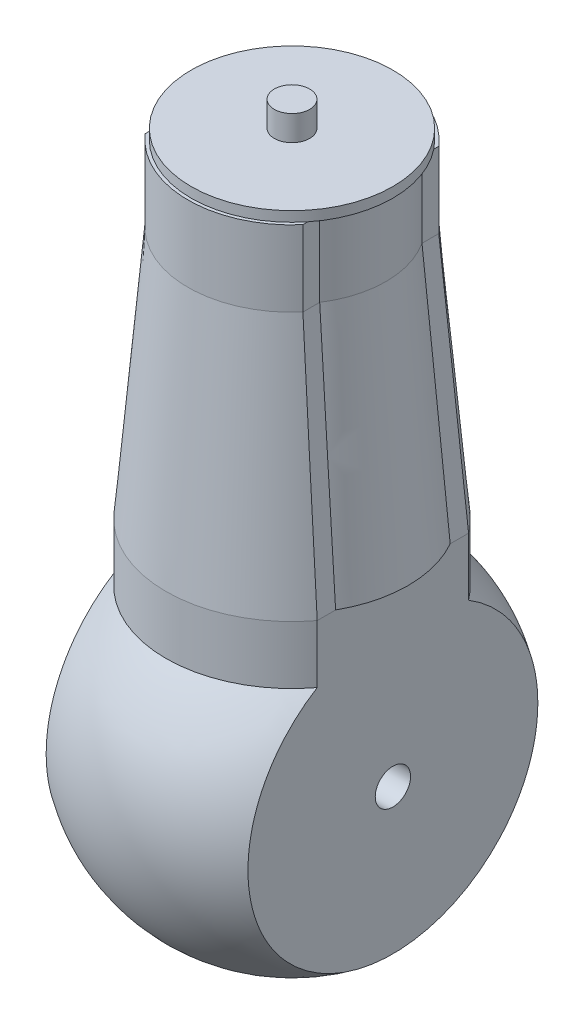
SolidWorks part; units mm, degrees
ref_plane "Front Plane" through (0, 0, 0) normal (0, 0, 1) x (1, 0, 0)
ref_plane "Top Plane" through (0, 0, 0) normal (0, 1, 0) x (1, 0, 0)
ref_plane "Right Plane" through (0, 0, 0) normal (1, 0, 0) x (0, 0, -1)
sketch "Sketch1" plane through (0, 0, 0) normal (0, 1, 0) x (1, 0, 0)
  line L0 (0, 35) -> (0, -35) construction
  line L1 (0, 35) -> (0, -35)
  arc A0 (0, -35) -> (0, 35) centre (0, 0) ccw
  dimension "D1" = 70
revolve "Revolve2" add sketch "Sketch1" angle 360 about L0
sketch "Sketch2" plane through (0, 0, 0) normal (0, 1, 0) x (1, 0, 0)
  line L2 (-20, -28.7228) -> (-20, 28.7228)
  line L4 (20, -28.7228) -> (20, 28.7228)
  line L5 (-20, -35) -> (20, 35) construction
  line L6 (-20, 35) -> (20, -35) construction
  arc A0 (20, 28.7228) -> (-20, 28.7228) centre (0, 0) ccw
  arc A1 (-20, -28.7228) -> (20, -28.7228) centre (0, 0) ccw
  dimension "D1" = 40
extrude "Cut-Extrude1" cut sketch "Sketch2" against normal up to next and the other way up to next flip side to cut
sketch "Sketch3" plane through (0, 0, 0) normal (0, 1, 0) x (1, 0, 0)
  line L4 (20, -28.7228) -> (20, 28.7228) construction
  line L6 (-20, 15) -> (-20, -15)
  line L8 (20, 15) -> (20, -15)
  line L9 (-20, 26.2775) -> (20, -26.2775) construction
  line L10 (-20, -26.2775) -> (20, 26.2775) construction
  arc A3 (20, 15) -> (-20, 15) centre (0, 0) ccw
  arc A4 (-20, -15) -> (20, -15) centre (0, 0) ccw
  arc A6 (-20, -28.7228) -> (20, -28.7228) centre (0, 0) ccw construction
  dimension "D1" = 50
  dimension "D2" = 10
extrude "Boss-Extrude1" add sketch "Sketch3" along normal blind 36
sketch "Sketch4" plane through (-20, 0, 0) normal (-1, 0, 0) x (0, 0, 1)
  circle A0 centre (0, 0) radius 3.5
  dimension "D1" = 7
extrude "Cut-Extrude2" cut sketch "Sketch4" against normal blind 5
pattern_linear "LPattern1" count 2 spacing 35 along (1, 0, 0) of "Cut-Extrude2"
sketch "Sketch5" plane through (0, 36, 0) normal (0, 1, 0) x (1, 0, 0)
  line L0 (-20, 15) -> (-20, 11.3578)
  line L1 (-20, 15) -> (-20, -15) construction
  line L2 (-20, -15) -> (-20, -11.3578)
  line L3 (20, 15) -> (20, 11.3578)
  line L4 (20, -11.3578) -> (20, -15)
  arc A0 (-20, -15) -> (20, -15) centre (0, 0) ccw
  arc A1 (20, -11.3578) -> (20, 11.3578) centre (0, 0) ccw
  arc A2 (20, 15) -> (-20, 15) centre (0, 0) ccw
  arc A3 (-20, 11.3578) -> (-20, -11.3578) centre (0, 0) ccw
  dimension "D2" = 46
extrude "Boss-Extrude2" add sketch "Sketch5" along normal blind 50 draft 5
sketch "Sketch9" plane through (0, 86, 0) normal (0, 1, 0) x (1, 0, 0)
  line L4 (15.6256, 10.1367) -> (15.6256, 13.4631)
  line L5 (-15.6256, 13.4631) -> (-15.6256, 10.1367)
  line L6 (-15.6256, -10.1367) -> (-15.6256, -13.4631)
  line L7 (15.6256, -13.4631) -> (15.6256, -10.1367)
  line L8 (15.6256, 10.1367) -> (15.6256, 13.4631)
  line L9 (-15.6256, 13.4631) -> (-15.6256, 10.1367)
  line L10 (-15.6256, -10.1367) -> (-15.6256, -13.4631)
  line L11 (15.6256, -13.4631) -> (15.6256, -10.1367)
  arc A4 (15.6256, -10.1367) -> (15.6256, 10.1367) centre (0, 0) ccw
  arc A5 (15.6256, 13.4631) -> (-15.6256, 13.4631) centre (0, 0) ccw
  arc A6 (-15.6256, 10.1367) -> (-15.6256, -10.1367) centre (0, 0) ccw
  arc A7 (-15.6256, -13.4631) -> (15.6256, -13.4631) centre (0, 0) ccw
  arc A8 (15.6256, -10.1367) -> (15.6256, 10.1367) centre (0, 0) ccw
  arc A9 (15.6256, 13.4631) -> (-15.6256, 13.4631) centre (0, 0) ccw
  arc A10 (-15.6256, 10.1367) -> (-15.6256, -10.1367) centre (0, 0) ccw
  arc A11 (-15.6256, -13.4631) -> (15.6256, -13.4631) centre (0, 0) ccw
  dimension "D1" = 0
extrude "Boss-Extrude6" add sketch "Sketch9" along normal blind 15
sketch "Sketch10" plane through (0, 101, 0) normal (0, 1, 0) x (1, 0, 0)
  circle A0 centre (0, 0) radius 20
  dimension "D1" = 40
extrude "Boss-Extrude7" add sketch "Sketch10" along normal blind 2
sketch "Sketch11" plane through (0, 103, 0) normal (0, 1, 0) x (1, 0, 0)
  circle A0 centre (0, 0) radius 3.5
  dimension "D1" = 7
extrude "Boss-Extrude8" add sketch "Sketch11" along normal blind 5
